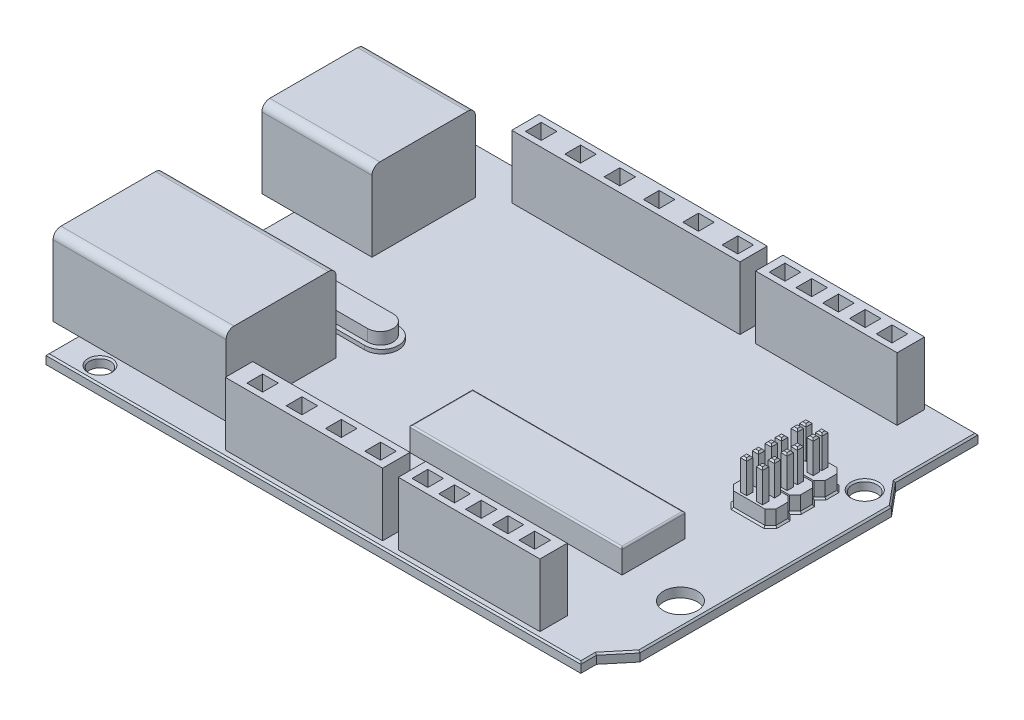
SolidWorks part; units mm, degrees
ref_plane "Front Plane" through (0, 0, 0) normal (0, 0, 1) x (1, 0, 0)
ref_plane "Top Plane" through (0, 0, 0) normal (0, 1, 0) x (1, 0, 0)
ref_plane "Right Plane" through (0, 0, 0) normal (1, 0, 0) x (0, 0, -1)
sketch "Sketch1" plane through (0, 0, 0) normal (0, 1, 0) x (1, 0, 0)
  line L0 (34, -23.25) -> (36.5, -20.25)
  line L1 (-34, -25.25) -> (34, -25.25)
  line L2 (-34, -25.25) -> (-34, 25.25)
  line L3 (-34, 25.25) -> (34, 25.25)
  line L4 (34, -25.25) -> (34, 25.25) construction
  line L5 (-34, -25.25) -> (34, 25.25) construction
  line L6 (-34, 25.25) -> (34, -25.25) construction
  line L7 (36.5, -20.25) -> (36.5, 11.75)
  line L8 (36.5, 11.75) -> (34, 14.75)
  line L9 (34, 14.75) -> (34, 25.25)
  line L10 (34, -23.25) -> (34, -25.25)
  point P0 (0, 0)
  dimension "D1" = 68
  dimension "D2" = 50.5
  dimension "D3" = 2.5
  dimension "D4" = 2
  dimension "D5" = 5
  dimension "D6" = 40
extrude "Boss-Extrude1" add sketch "Sketch1" along normal blind 1.2
sketch "Sketch2" plane through (0, 1.2, 0) normal (0, 1, 0) x (1, 0, 0)
  line L0 (-34, -25.25) -> (34, -25.25) construction
  line L1 (-12, -20.97) -> (8, -20.97)
  line L2 (-12, -20.97) -> (-12, -24.45)
  line L3 (-12, -24.45) -> (8, -24.45)
  line L4 (8, -20.97) -> (8, -24.45)
  line L5 (-34, 25.25) -> (-34, -25.25) construction
  line L6 (-34, 0) -> (36.5, 0) construction
  line L7 (10, -20.97) -> (28, -20.97)
  line L8 (10, -20.97) -> (10, -24.45)
  line L9 (10, -24.45) -> (28, -24.45)
  line L10 (28, -20.97) -> (28, -24.45)
  line L11 (36.5, -20.25) -> (36.5, 11.75) construction
  line L12 (28, 20.97) -> (28, 24.45)
  line L13 (10, 24.45) -> (28, 24.45)
  line L14 (10, 20.97) -> (10, 24.45)
  line L15 (10, 20.97) -> (28, 20.97)
  line L16 (8, 20.97) -> (8, 24.45)
  line L17 (-12, 24.45) -> (8, 24.45)
  line L18 (-12, 20.97) -> (-12, 24.45) construction
  line L19 (-12, 20.97) -> (8, 20.97)
  line L20 (-12, 24.45) -> (-21, 24.45)
  line L21 (-21, 24.45) -> (-21, 20.97)
  line L22 (-21, 20.97) -> (-12, 20.97)
  point P6 (-12, -22.71)
  dimension "D1" = 0.8
  dimension "D2" = 2.54
  dimension "D3" = 42
  dimension "D4" = 12
  dimension "D5" = 18
  dimension "D6" = 2
  dimension "D7" = 9
extrude "Boss-Extrude2" add sketch "Sketch2" along normal blind 8 separate body
sketch "Sketch3" plane through (0, 9.2, 0) normal (0, 1, 0) x (1, 0, 0)
  line L0 (10, -20.97) -> (10, -24.45) construction
  line L1 (10, -24.45) -> (28, -24.45) construction
  line L2 (28, -24.45) -> (28, -20.97) construction
  line L3 (28, -20.97) -> (10, -20.97) construction
  line L4 (-21, 20.97) -> (8, 20.97)
  line L5 (8, 20.97) -> (8, 24.45)
  line L6 (8, 24.45) -> (-21, 24.45)
  line L7 (-21, 24.45) -> (-21, 20.97)
  line L8 (-21, 20.97) -> (8, 20.97) construction
  line L9 (8, 20.97) -> (8, 24.45) construction
  line L10 (8, 24.45) -> (-21, 24.45) construction
  line L11 (-21, 24.45) -> (-21, 20.97) construction
  line L12 (-12, -20.97) -> (-12, -24.45) construction
  line L13 (-12, -24.45) -> (8, -24.45) construction
  line L14 (8, -24.45) -> (8, -20.97) construction
  line L15 (8, -20.97) -> (-12, -20.97) construction
  line L16 (10, 20.97) -> (28, 20.97) construction
  line L17 (28, 20.97) -> (28, 24.45) construction
  line L18 (28, 24.45) -> (10, 24.45) construction
  line L19 (10, 24.45) -> (10, 20.97) construction
  line L20 (10, -20.97) -> (10, -24.45) construction
  line L21 (10, -24.45) -> (28, -24.45) construction
  line L22 (28, -24.45) -> (28, -20.97) construction
  line L23 (28, -20.97) -> (10, -20.97) construction
  line L24 (-12, -20.97) -> (-12, -24.45) construction
  line L25 (-12, -24.45) -> (8, -24.45) construction
  line L26 (8, -24.45) -> (8, -20.97) construction
  line L27 (8, -20.97) -> (-12, -20.97) construction
  line L28 (10, 20.97) -> (28, 20.97) construction
  line L29 (28, 20.97) -> (28, 24.45) construction
  line L30 (28, 24.45) -> (10, 24.45) construction
  line L31 (10, 24.45) -> (10, 20.97) construction
  line L32 (-21, 22.71) -> (8, 22.71) construction
  line L33 (-13, 23.71) -> (-13, 21.71)
  line L34 (-20, 23.71) -> (-18, 23.71)
  line L35 (-20, 23.71) -> (-20, 21.71)
  line L36 (-20, 21.71) -> (-18, 21.71)
  line L37 (-18, 23.71) -> (-18, 21.71)
  line L38 (-20, 23.71) -> (-18, 21.71) construction
  line L39 (-20, 21.71) -> (-18, 23.71) construction
  line L40 (-15, 21.71) -> (-13, 21.71)
  line L41 (-15, 23.71) -> (-15, 21.71)
  line L42 (-15, 23.71) -> (-13, 23.71)
  line L43 (-8, 23.71) -> (-8, 21.71)
  line L44 (-10, 21.71) -> (-8, 21.71)
  line L45 (-10, 23.71) -> (-10, 21.71)
  line L46 (-10, 23.71) -> (-8, 23.71)
  line L47 (-3, 23.71) -> (-3, 21.71)
  line L48 (-5, 21.71) -> (-3, 21.71)
  line L49 (-5, 23.71) -> (-5, 21.71)
  line L50 (-5, 23.71) -> (-3, 23.71)
  line L51 (2, 23.71) -> (2, 21.71)
  line L52 (0, 21.71) -> (2, 21.71)
  line L53 (0, 23.71) -> (0, 21.71)
  line L54 (0, 23.71) -> (2, 23.71)
  line L55 (7, 23.71) -> (7, 21.71)
  line L56 (5, 21.71) -> (7, 21.71)
  line L57 (5, 23.71) -> (5, 21.71)
  line L58 (5, 23.71) -> (7, 23.71)
  line L59 (-18, 23.71) -> (-13, 23.71) construction
  line L60 (10, 22.71) -> (28, 22.71) construction
  line L61 (16.4, 21.71) -> (16.4, 23.71)
  line L62 (11, 21.71) -> (13, 21.71)
  line L63 (11, 21.71) -> (11, 23.71)
  line L64 (11, 23.71) -> (13, 23.71)
  line L65 (13, 21.71) -> (13, 23.71)
  line L66 (11, 21.71) -> (13, 23.71) construction
  line L67 (11, 23.71) -> (13, 21.71) construction
  line L68 (14.4, 21.71) -> (16.4, 21.71)
  line L69 (14.4, 21.71) -> (14.4, 23.71)
  line L70 (14.4, 23.71) -> (16.4, 23.71)
  line L71 (13.4, 22.71) -> (31.4, 22.71) construction
  line L72 (19.8, 21.71) -> (19.8, 23.71)
  line L73 (17.8, 21.71) -> (19.8, 21.71)
  line L74 (17.8, 21.71) -> (17.8, 23.71)
  line L75 (17.8, 23.71) -> (19.8, 23.71)
  line L76 (16.8, 22.71) -> (34.8, 22.71) construction
  line L77 (23.2, 21.71) -> (23.2, 23.71)
  line L78 (21.2, 21.71) -> (23.2, 21.71)
  line L79 (21.2, 21.71) -> (21.2, 23.71)
  line L80 (21.2, 23.71) -> (23.2, 23.71)
  line L81 (20.2, 22.71) -> (38.2, 22.71) construction
  line L82 (26.6, 21.71) -> (26.6, 23.71)
  line L83 (24.6, 21.71) -> (26.6, 21.71)
  line L84 (24.6, 21.71) -> (24.6, 23.71)
  line L85 (24.6, 23.71) -> (26.6, 23.71)
  line L86 (23.6, 22.71) -> (41.6, 22.71) construction
  line L87 (13, 21.71) -> (16.4, 21.71) construction
  line L88 (-34, 0) -> (36.5, 0) construction
  line L89 (-34, 25.25) -> (-34, -25.25) construction
  line L90 (36.5, -20.25) -> (36.5, 11.75) construction
  line L91 (13, -21.71) -> (16.4, -21.71) construction
  line L92 (23.6, -22.71) -> (41.6, -22.71) construction
  line L93 (20.2, -22.71) -> (38.2, -22.71) construction
  line L94 (16.8, -22.71) -> (34.8, -22.71) construction
  line L95 (13.4, -22.71) -> (31.4, -22.71) construction
  line L96 (11, -23.71) -> (13, -21.71) construction
  line L97 (11, -21.71) -> (13, -23.71) construction
  line L98 (10, -22.71) -> (28, -22.71) construction
  line L102 (-21, -22.71) -> (8, -22.71) construction
  line L103 (10, -24.45) -> (10, -20.97) construction
  line L104 (28, -24.45) -> (10, -24.45) construction
  line L105 (28, -20.97) -> (28, -24.45) construction
  line L106 (10, -20.97) -> (28, -20.97) construction
  line L107 (-21, -24.45) -> (-21, -20.97) construction
  line L108 (8, -24.45) -> (-21, -24.45) construction
  line L109 (8, -20.97) -> (8, -24.45) construction
  line L110 (-21, -20.97) -> (8, -20.97) construction
  line L111 (24.6, -23.71) -> (26.6, -23.71)
  line L112 (24.6, -21.71) -> (24.6, -23.71)
  line L113 (24.6, -21.71) -> (26.6, -21.71)
  line L114 (26.6, -21.71) -> (26.6, -23.71)
  line L115 (21.2, -23.71) -> (23.2, -23.71)
  line L116 (21.2, -21.71) -> (21.2, -23.71)
  line L117 (21.2, -21.71) -> (23.2, -21.71)
  line L118 (23.2, -21.71) -> (23.2, -23.71)
  line L119 (17.8, -23.71) -> (19.8, -23.71)
  line L120 (17.8, -21.71) -> (17.8, -23.71)
  line L121 (17.8, -21.71) -> (19.8, -21.71)
  line L122 (19.8, -21.71) -> (19.8, -23.71)
  line L123 (14.4, -23.71) -> (16.4, -23.71)
  line L124 (14.4, -21.71) -> (14.4, -23.71)
  line L125 (14.4, -21.71) -> (16.4, -21.71)
  line L126 (13, -21.71) -> (13, -23.71)
  line L127 (11, -23.71) -> (13, -23.71)
  line L128 (11, -21.71) -> (11, -23.71)
  line L129 (11, -21.71) -> (13, -21.71)
  line L130 (16.4, -21.71) -> (16.4, -23.71)
  line L131 (5, -23.71) -> (7, -23.71)
  line L132 (5, -23.71) -> (5, -21.71)
  line L133 (5, -21.71) -> (7, -21.71)
  line L134 (7, -23.71) -> (7, -21.71)
  line L135 (0, -23.71) -> (2, -23.71)
  line L136 (0, -23.71) -> (0, -21.71)
  line L137 (0, -21.71) -> (2, -21.71)
  line L138 (2, -23.71) -> (2, -21.71)
  line L139 (-5, -23.71) -> (-3, -23.71)
  line L140 (-5, -23.71) -> (-5, -21.71)
  line L141 (-5, -21.71) -> (-3, -21.71)
  line L142 (-3, -23.71) -> (-3, -21.71)
  line L143 (-10, -23.71) -> (-8, -23.71)
  line L144 (-10, -23.71) -> (-10, -21.71)
  line L145 (-10, -21.71) -> (-8, -21.71)
  line L146 (-8, -23.71) -> (-8, -21.71)
  point P10 (-19, 22.71)
  point P47 (12, 22.71)
  point P155 (12, -22.71)
  point P156 (-19, -22.71)
  dimension "D2" = 1
  dimension "D3" = 2
  dimension "D4" = 2
  dimension "D6" = 5
  dimension "D7" = 1
  dimension "D9" = 3.4
  dimension "D1" = 0
  dimension "D5" = 6
  dimension "D8" = 5
extrude "Cut-Extrude1" cut sketch "Sketch3" against normal blind 6
sketch "Sketch4" plane through (0, 1.2, 0) normal (0, 1, 0) x (1, 0, 0)
  line L1 (-37.9, 19.25) -> (-23.9, 19.25)
  line L2 (-37.9, 19.25) -> (-37.9, 6.1)
  line L3 (-37.9, 6.1) -> (-23.9, 6.1)
  line L4 (-23.9, 19.25) -> (-23.9, 6.1)
  line L5 (-34, 25.25) -> (-34, -25.25) construction
  line L6 (34, 25.25) -> (-34, 25.25) construction
  line L7 (-34, -25.25) -> (34, -25.25) construction
  line L8 (-37.1, -7.25) -> (-15.1, -7.25)
  line L9 (-37.1, -7.25) -> (-37.1, -21.25)
  line L10 (-37.1, -21.25) -> (-15.1, -21.25)
  line L11 (-15.1, -7.25) -> (-15.1, -21.25)
  dimension "D1" = 6
  dimension "D2" = 13.15
  dimension "D3" = 3.9
  dimension "D4" = 14
  dimension "D5" = 14
  dimension "D6" = 4
  dimension "D7" = 22
  dimension "D8" = 3.1
extrude "Boss-Extrude3" add sketch "Sketch4" along normal blind 10 separate body
fillet "Fillet1" radius 1 2 edges at (-30.9, 11.2, -19.25) (-30.9, 11.2, -6.1)
fillet "Fillet2" radius 1 2 edges at (-26.1, 11.2, 7.25) (-26.1, 11.2, 21.25)
sketch "Sketch5" plane through (-37.9, 0, 0) normal (-1, 0, 0) x (0, 0, 1)
  line L0 (7.25, 5.7) -> (14.25, 5.7) construction
  line L1 (-16.175, 9.2) -> (-9.175, 9.2)
  line L2 (-16.175, 9.2) -> (-16.175, 2.2)
  line L3 (-16.175, 2.2) -> (-9.175, 2.2)
  line L4 (-9.175, 9.2) -> (-9.175, 2.2)
  line L5 (-16.175, 9.2) -> (-9.175, 2.2) construction
  line L6 (-16.175, 2.2) -> (-9.175, 9.2) construction
  line L7 (9.75, 7.7) -> (18.75, 7.7)
  line L8 (9.75, 7.7) -> (9.75, 3.7)
  line L9 (9.75, 3.7) -> (18.75, 3.7)
  line L10 (18.75, 7.7) -> (18.75, 3.7)
  line L11 (9.75, 7.7) -> (18.75, 3.7) construction
  line L12 (9.75, 3.7) -> (18.75, 7.7) construction
  line L13 (7.25, 10.2) -> (7.25, 1.2) construction
  line L14 (14.25, 11.2) -> (14.25, 5.7) construction
  line L15 (8.25, 11.2) -> (20.25, 11.2) construction
  line L16 (-19.25, 5.7) -> (-12.675, 5.7) construction
  line L17 (-19.25, 10.2) -> (-19.25, 1.2) construction
  line L18 (-12.675, 5.7) -> (-12.675, 11.2) construction
  line L19 (-18.25, 11.2) -> (-7.1, 11.2) construction
  point P0 (-12.675, 5.7)
  point P5 (14.25, 5.7)
  dimension "D1" = 9
  dimension "D2" = 4
  dimension "D3" = 7
extrude "Cut-Extrude2" cut sketch "Sketch5" against normal blind 12
sketch "Sketch6" plane through (-25.9, 0, 0) normal (-1, 0, 0) x (0, 0, 1)
  line L4 (18.75, 3.7) -> (18.75, 7.7)
  line L5 (18.75, 7.7) -> (9.75, 7.7)
  line L6 (9.75, 7.7) -> (9.75, 3.7)
  line L7 (9.75, 3.7) -> (18.75, 3.7)
  line L8 (18.75, 3.7) -> (18.75, 7.7)
  line L9 (18.75, 7.7) -> (9.75, 7.7)
  line L10 (9.75, 7.7) -> (9.75, 3.7)
  line L11 (9.75, 3.7) -> (18.75, 3.7)
  dimension "D1" = 0
extrude "Cut-Extrude3" cut sketch "Sketch6" against normal blind 7.5
sketch "Sketch7" plane through (0, 1.2, 0) normal (0, 1, 0) x (1, 0, 0)
  line L0 (0, 0) -> (0, -25.25) construction
  line L1 (0, -5) -> (27, -5)
  line L2 (0, -5) -> (0, -13)
  line L3 (0, -13) -> (27, -13)
  line L4 (27, -5) -> (27, -13)
  line L5 (-34, -25.25) -> (34, -25.25) construction
  dimension "D1" = 27
  dimension "D2" = 8
  dimension "D3" = 5
extrude "Boss-Extrude4" add sketch "Sketch7" along normal blind 3 separate body
fillet "Fillet3" radius 0.2 4 edges at (13.5, 4.2, 5) (27, 4.2, 9) (13.5, 4.2, 13) (0, 4.2, 9)
sketch "Sketch9" plane through (-25.9, 0.3059, -0.0931) normal (-1, 0, 0) x (0, 0, 1)
  line L1 (-14.4711, 5.956) -> (-10.3474, 5.956)
  line L2 (-14.4711, 5.956) -> (-14.4711, 3.7822)
  line L3 (-14.4711, 3.7822) -> (-10.3474, 3.7822)
  line L4 (-10.3474, 5.956) -> (-10.3474, 3.7822)
extrude "Boss-Extrude7" add sketch "Sketch9" along normal blind 10
sketch "Sketch10" plane through (0, 1.2, 0) normal (0, 1, 0) x (1, 0, 0)
  circle A0 centre (-29.2788, -23.1125) radius 1.3264
extrude "Cut-Extrude4" cut sketch "Sketch10" against normal blind 3
sketch "Sketch11" plane through (0, 1.2, 0) normal (0, 1, 0) x (1, 0, 0)
  circle A0 centre (33.0537, 11.7964) radius 1.5637
extrude "Cut-Extrude6" cut sketch "Sketch11" against normal blind 3
sketch "Sketch13" plane through (0, 1.2, 0) normal (0, 1, 0) x (1, 0, 0)
  line L8 (26.7929, 10.4979) -> (30.7929, 10.4979)
  line L9 (30.7929, 10.4979) -> (31.5, 9.7908)
  line L10 (31.5, 9.7908) -> (31.5, 8.2908)
  line L11 (31.5, 8.2908) -> (30.7929, 7.5837)
  line L12 (30.7929, 7.5837) -> (26.7929, 7.5837)
  line L13 (26.7929, 7.5837) -> (26.0858, 8.2908)
  line L14 (26.0858, 8.2908) -> (26.0858, 9.7908)
  line L15 (26.0858, 9.7908) -> (26.7929, 10.4979)
  line L34 (26.0858, 6.6766) -> (26.0858, 5.1766)
  line L35 (26.7929, 7.3837) -> (26.0858, 6.6766)
  line L36 (30.7929, 7.3837) -> (26.7929, 7.3837)
  line L37 (31.5, 6.6766) -> (30.7929, 7.3837)
  line L38 (31.5, 5.1766) -> (31.5, 6.6766)
  line L39 (30.7929, 4.4695) -> (31.5, 5.1766)
  line L40 (26.7929, 4.4695) -> (30.7929, 4.4695)
  line L41 (26.0858, 5.1766) -> (26.7929, 4.4695)
  line L42 (26.7929, 1.3553) -> (26.0858, 2.0624)
  line L43 (30.7929, 1.3553) -> (26.7929, 1.3553)
  line L44 (31.5, 2.0624) -> (30.7929, 1.3553)
  line L45 (31.5, 3.5624) -> (31.5, 2.0624)
  line L46 (30.7929, 4.2695) -> (31.5, 3.5624)
  line L47 (26.7929, 4.2695) -> (30.7929, 4.2695)
  line L48 (26.0858, 3.5624) -> (26.7929, 4.2695)
  line L49 (26.0858, 2.0624) -> (26.0858, 3.5624)
extrude "Boss-Extrude8" add sketch "Sketch13" along normal blind 2
sketch "Sketch15" plane through (0, 3.2, 0) normal (0, 1, 0) x (1, 0, 0)
  line L9 (27.3858, 9.9837) -> (28.1858, 9.9837)
  line L10 (27.3858, 9.9837) -> (27.3858, 9.1837)
  line L11 (27.3858, 9.1837) -> (28.1858, 9.1837)
  line L12 (28.1858, 9.9837) -> (28.1858, 9.1837)
  line L17 (29.4, 9.9837) -> (30.2, 9.9837)
  line L18 (29.4, 9.9837) -> (29.4, 9.1837)
  line L19 (29.4, 9.1837) -> (30.2, 9.1837)
  line L20 (30.2, 9.9837) -> (30.2, 9.1837)
  line L21 (27.3858, 8.8837) -> (28.1858, 8.8837)
  line L22 (27.3858, 8.8837) -> (27.3858, 8.0837)
  line L23 (27.3858, 8.0837) -> (28.1858, 8.0837)
  line L24 (28.1858, 8.8837) -> (28.1858, 8.0837)
  line L25 (29.4, 8.8837) -> (30.2, 8.8837)
  line L26 (29.4, 8.8837) -> (29.4, 8.0837)
  line L27 (29.4, 8.0837) -> (30.2, 8.0837)
  line L28 (30.2, 8.8837) -> (30.2, 8.0837)
extrude "Boss-Extrude9" add sketch "Sketch15" along normal blind 4
chamfer "Chamfer5" distance 0.2 angle 45 1 edges at (27.7858, 7.2, -9.9837)
chamfer "Chamfer6" distance 0.2 angle 45 1 edges at (27.7858, 7.2, -9.1837)
chamfer "Chamfer7" distance 0.2 angle 45 1 edges at (28.1858, 7.2, -9.5837)
chamfer "Chamfer8" distance 0.2 angle 45 1 edges at (27.3858, 7.2, -9.5837)
chamfer "Chamfer9" distance 0.2 angle 45 4 edges at (29.8, 7.2, -9.9837) (29.4, 7.2, -9.5837) (29.8, 7.2, -9.1837) (30.2, 7.2, -9.5837)
chamfer "Chamfer10" distance 0.2 angle 45 8 edges at (27.7858, 7.2, -8.0837) (27.3858, 7.2, -8.4837) (27.7858, 7.2, -8.8837) (28.1858, 7.2, -8.4837) (29.8, 7.2, -8.8837) (29.4, 7.2, -8.4837) (29.8, 7.2, -8.0837) (30.2, 7.2, -8.4837)
sketch "Sketch18" plane through (0, 3.2, 0) normal (0, 1, 0) x (1, 0, 0)
  line L5 (29.3958, 6.8837) -> (30.1958, 6.8837)
  line L6 (29.3958, 6.8837) -> (29.3958, 6.085)
  line L7 (29.3958, 6.085) -> (30.1958, 6.085)
  line L8 (30.1958, 6.8837) -> (30.1958, 6.085)
  line L21 (27.3858, 6.8837) -> (28.1858, 6.8837)
  line L22 (27.3858, 6.8837) -> (27.3858, 6.0837)
  line L23 (27.3858, 6.0837) -> (28.1858, 6.0837)
  line L24 (28.1858, 6.8837) -> (28.1858, 6.0837)
  line L33 (27.3858, 5.5837) -> (27.3858, 4.7837)
  line L34 (29.3958, 5.5837) -> (30.1958, 5.5837)
  line L35 (27.3858, 5.5837) -> (28.1858, 5.5837)
  line L36 (28.1858, 5.5837) -> (28.1858, 4.7837)
  line L37 (27.3858, 4.7837) -> (28.1858, 4.7837)
  line L38 (29.3958, 5.5837) -> (29.3958, 4.7837)
  line L39 (29.3958, 4.7837) -> (30.1958, 4.7837)
  line L40 (30.1958, 5.5837) -> (30.1958, 4.7837)
  dimension "D2" = 2
extrude "Boss-Extrude11" add sketch "Sketch18" along normal blind 4
chamfer "Chamfer11" distance 0.2 angle 45 42 edges at (31.1464, 1.2, -1.7089) (31.5, 1.2, -2.8124) (31.1464, 1.2, -3.916) (28.7929, 1.2, -4.2695) (26.4393, 1.2, -3.916) (26.0858, 1.2, -2.8124) (26.4393, 1.2, -1.7089) (28.7929, 1.2, -1.3553) (26.0858, 1.2, -9.0408) (26.4393, 1.2, -7.9373) (28.7929, 1.2, -7.5837) (31.1464, 1.2, -7.9373) (31.5, 1.2, -9.0408) (31.1464, 1.2, -10.1444) (28.7929, 1.2, -10.4979) (26.4393, 1.2, -10.1444) (33.0537, 1.2, -10.2327) (-29.2788, 1.2, 24.439) (35.25, 1.2, -13.25) (36.5, 1.2, 4.25) (35.25, 1.2, 21.75) (34, 1.2, 24.25) (0, 1.2, 25.25) (-34, 1.2, 0) (0, 1.2, -25.25) (34, 1.2, -20) (26.0858, 1.2, -5.9266) (26.4393, 1.2, -4.8231) (28.7929, 1.2, -4.4695) (31.1464, 1.2, -4.8231) (31.5, 1.2, -5.9266) (31.1464, 1.2, -7.0302) (28.7929, 1.2, -7.3837) (26.4393, 1.2, -7.0302) (29.3958, 7.2, -6.4843) (29.7958, 7.2, -6.085) (30.1958, 7.2, -6.4843) (29.7958, 7.2, -6.8837) (27.3858, 7.2, -6.4837) (27.7858, 7.2, -6.0837) (28.1858, 7.2, -6.4837) (27.7858, 7.2, -6.8837)
chamfer "Chamfer12" distance 0.2 angle 45 8 edges at (30.1958, 7.2, -5.1837) (29.7958, 7.2, -4.7837) (29.3958, 7.2, -5.1837) (29.7958, 7.2, -5.5837) (27.3858, 7.2, -5.1837) (27.7858, 7.2, -4.7837) (28.1858, 7.2, -5.1837) (27.7858, 7.2, -5.5837)
sketch "Sketch19" plane through (0, 3.2, 0) normal (0, 1, 0) x (1, 0, 0)
  line L1 (27.3858, 3.9695) -> (28.1858, 3.9695)
  line L2 (27.3858, 3.9695) -> (27.3858, 3.1695)
  line L3 (27.3858, 3.1695) -> (28.1858, 3.1695)
  line L4 (28.1858, 3.9695) -> (28.1858, 3.1695)
  line L6 (27.3858, 2.4553) -> (27.3858, 1.6553)
  line L7 (27.3858, 2.4553) -> (28.1858, 2.4553)
  line L8 (28.1858, 2.4553) -> (28.1858, 1.6553)
  line L9 (27.3858, 1.6553) -> (28.1858, 1.6553)
  line L13 (29.4017, 3.9695) -> (30.1984, 3.9695)
  line L14 (29.4017, 3.9695) -> (29.4017, 3.1695)
  line L15 (29.4017, 3.1695) -> (30.1984, 3.1695)
  line L16 (30.1984, 3.9695) -> (30.1984, 3.1695)
  line L17 (29.4017, 2.4553) -> (30.1984, 2.4553)
  line L18 (29.4017, 2.4553) -> (29.4017, 1.6553)
  line L19 (29.4017, 1.6553) -> (30.1984, 1.6553)
  line L20 (30.1984, 2.4553) -> (30.1984, 1.6553)
  dimension "D1" = 2
extrude "Boss-Extrude12" add sketch "Sketch19" along normal blind 4
chamfer "Chamfer14" distance 0.2 angle 45 16 edges at (29.4017, 7.2, -2.0553) (29.8, 7.2, -1.6553) (30.1984, 7.2, -2.0553) (29.8, 7.2, -2.4553) (27.7858, 7.2, -1.6553) (27.3858, 7.2, -2.0553) (28.1858, 7.2, -2.0553) (27.7858, 7.2, -2.4553) (29.8, 7.2, -3.1695) (30.1984, 7.2, -3.5695) (29.8, 7.2, -3.9695) (29.4017, 7.2, -3.5695) (28.1858, 7.2, -3.5695) (27.7858, 7.2, -3.1695) (27.3858, 7.2, -3.5695) (27.7858, 7.2, -3.9695)
sketch "Sketch20" plane through (0, 1.2, 0) normal (0, 1, 0) x (1, 0, 0)
  text T0 "<b><i>Arduino Uno </i></b>\r\n<b><i>KELOMPOK 16</i></b>" font "Clarendon Blk BT" height in points 9
sketch "Sketch22" plane through (0, 1.2, 0) normal (0, 1, 0) x (1, 0, 0)
  line L7 (-22.0645, -0.2915) -> (-14.1524, -0.2915)
  line L9 (-22.0645, -4.5705) -> (-14.1524, -4.5705)
  arc A2 (-14.1524, -4.5705) -> (-14.1524, -0.2915) centre (-14.1524, -2.431) ccw
  arc A3 (-22.0645, -0.2915) -> (-22.0645, -4.5705) centre (-22.0645, -2.431) ccw
extrude "Boss-Extrude14" add sketch "Sketch22" along normal blind 0.5
sketch "Sketch24" plane through (0, 1.7, 0) normal (0, 1, 0) x (1, 0, 0)
  line L1 (-21.8011, -0.7777) -> (-14.3323, -0.7777)
  line L3 (-21.8011, -4.0263) -> (-14.3323, -4.0263)
  arc A0 (-21.8011, -0.7777) -> (-21.8011, -4.0263) centre (-21.8011, -2.402) ccw
  arc A1 (-14.3323, -4.0263) -> (-14.3323, -0.7777) centre (-14.3323, -2.402) ccw
extrude "Boss-Extrude16" add sketch "Sketch24" along normal blind 1.5
sketch "Sketch26" plane through (0, 1.2, 0) normal (0, 1, 0) x (1, 0, 0)
  circle A0 centre (33.5481, -12.129) radius 2.1564
extrude "Cut-Extrude7" cut sketch "Sketch26" against normal blind 10
